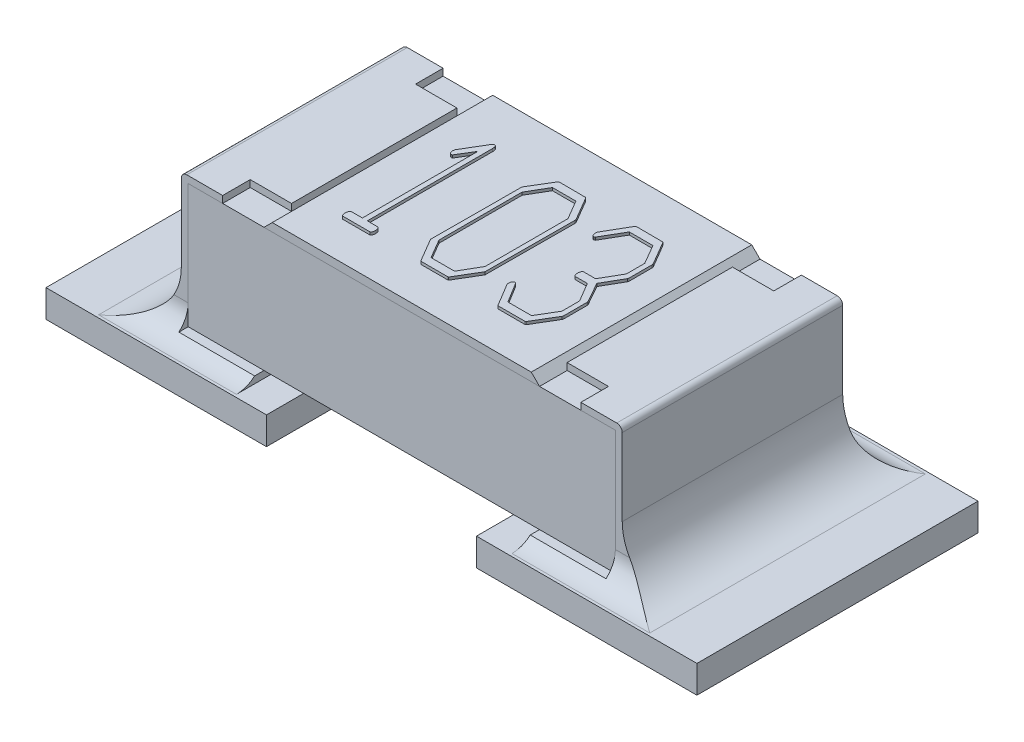
SolidWorks part; units mm, degrees
material "Ceramic Porcelain"
ref_plane "Front Plane" through (0, 0, 0) normal (0, 0, 1) x (1, 0, 0)
ref_plane "Top Plane" through (0, 0, 0) normal (0, 1, 0) x (1, 0, 0)
ref_plane "Right Plane" through (0, 0, 0) normal (1, 0, 0) x (0, 0, -1)
sketch "Sketch1" plane through (0, 0, 0) normal (1, 0, 0) x (0, 0, -1)
  line L0 (0, 55) -> (0, -55) construction
  line L1 (-0.4, 0.575) -> (0.4, 0.575)
  line L2 (-0.4, 0.575) -> (-0.4, 0.125)
  line L3 (-0.4, 0.125) -> (0.4, 0.125)
  line L4 (0.4, 0.575) -> (0.4, 0.125)
  line L5 (55, 0) -> (-55, 0) construction
  dimension "D1" = 0.8
  dimension "D2" = 0.4
  dimension "D3" = 0.45
  dimension "D4" = 0.125
extrude "Boss-Extrude1" add sketch "Sketch1" along normal mid plane 1.55
sketch "Sketch2" plane through (0, 0, 0) normal (0, 0, 1) x (1, 0, 0)
  line L0 (-0.5, 0.6) -> (-0.78, 0.6)
  line L1 (-0.8, 0.58) -> (-0.8, 0.1)
  line L2 (-0.8, 0.1) -> (-0.5, 0.1)
  line L3 (-0.5, 0.1) -> (-0.5, 0.125)
  line L4 (0.775, 0.125) -> (-0.775, 0.125) construction
  line L5 (-0.5, 0.125) -> (-0.775, 0.125)
  line L6 (-0.775, 0.125) -> (-0.775, 0.575)
  line L7 (-0.775, 0.575) -> (-0.5, 0.575)
  line L8 (0.775, 0.575) -> (-0.775, 0.575) construction
  line L9 (-0.5, 0.575) -> (-0.5, 0.6)
  line L11 (0.5, 0.575) -> (0.5, 0.6)
  line L12 (0.5, 0.6) -> (0.78, 0.6)
  line L13 (0.8, 0.58) -> (0.8, 0.1)
  line L14 (0.8, 0.1) -> (0.5, 0.1)
  line L15 (0.5, 0.1) -> (0.5, 0.125)
  line L16 (0.5, 0.125) -> (0.775, 0.125)
  line L17 (0.775, 0.125) -> (0.775, 0.575)
  line L18 (0.775, 0.575) -> (0.5, 0.575)
  arc A0 (0.78, 0.6) -> (0.8, 0.58) centre (0.78, 0.58) cw
  arc A1 (-0.78, 0.6) -> (-0.8, 0.58) centre (-0.78, 0.58) ccw
  point P28 (-0.8, 0.6)
  dimension "D6" = 0.02
  dimension "D1" = 0.025
  dimension "D2" = 0.025
  dimension "D3" = 0.025
  dimension "D4" = 0.3
  dimension "D5" = 0.3
extrude "Boss-Extrude2" add sketch "Sketch2" along normal mid plane 0.8 separate body
sketch "Sketch3" plane through (0, 0.6, 0) normal (0, 1, 0) x (1, 0, 0)
  line L0 (0.5, -0.4) -> (0.5, 0.4) construction
  line L1 (-0.5, 0.4) -> (-0.65, 0.4)
  line L2 (-0.5, 0.4) -> (-0.5, 0.3)
  line L3 (-0.5, 0.3) -> (-0.65, 0.3)
  line L4 (-0.65, 0.4) -> (-0.65, 0.3)
  line L5 (-0.5, -0.4) -> (-0.65, -0.4)
  line L6 (-0.5, -0.4) -> (-0.5, -0.3)
  line L7 (-0.5, -0.3) -> (-0.65, -0.3)
  line L8 (-0.65, -0.4) -> (-0.65, -0.3)
  line L9 (0.5, -0.4) -> (0.65, -0.4)
  line L10 (0.5, -0.4) -> (0.5, -0.3)
  line L11 (0.5, -0.3) -> (0.65, -0.3)
  line L12 (0.65, -0.4) -> (0.65, -0.3)
  line L13 (0.775, -0.4) -> (-0.775, -0.4) construction
  line L15 (0.5, 0.4) -> (0.65, 0.4)
  line L16 (0.5, 0.4) -> (0.5, 0.3)
  line L17 (0.5, 0.3) -> (0.65, 0.3)
  line L18 (0.65, 0.4) -> (0.65, 0.3)
  dimension "D1" = 0.15
  dimension "D2" = 0.1
extrude "Cut-Extrude1" cut sketch "Sketch3" against normal blind 0.025
sketch "Sketch4" plane through (0, 0, 0) normal (0, 0, 1) x (1, 0, 0)
  line L0 (-0.5, 0.575) -> (0.5, 0.575)
  line L1 (0.5, 0.575) -> (0.47, 0.605)
  line L2 (0.47, 0.605) -> (-0.47, 0.605)
  line L3 (-0.47, 0.605) -> (-0.5, 0.575)
  dimension "D1" = 45
  dimension "D2" = 45
  dimension "D3" = 0.03
extrude "Boss-Extrude3" add sketch "Sketch4" along normal mid plane 0.8 separate body
sketch "Sketch6" plane through (0, 0.605, 0) normal (0, 1, 0) x (1, 0, 0)
  line L0 (-0.4, -0.25) -> (0.4, -0.25) construction
  line L1 (0, -0.2777) -> (0, 0.2777) construction
  line L2 (-0.2777, 0) -> (0.2777, 0) construction
  text T0 "103\r\n" font "SWMono" height 0.5
  dimension "D1" = 0.8
  dimension "D2" = 0.4
  dimension "D3" = 0.25
extrude "Boss-Extrude4" add sketch "Sketch6" along normal blind 0.01
sketch "Sketch7" plane through (0, 0, 0) normal (0, 1, 0) x (1, 0, 0)
  line L0 (0, -0.2833) -> (0, 0.2833) construction
  line L1 (-0.381, -0.51) -> (-1.181, -0.51)
  line L2 (-0.381, -0.51) -> (-0.381, 0.51)
  line L3 (-0.381, 0.51) -> (-1.181, 0.51)
  line L4 (-1.181, -0.51) -> (-1.181, 0.51)
  line L5 (0.381, -0.51) -> (1.181, -0.51)
  line L6 (0.381, -0.51) -> (0.381, 0.51)
  line L7 (0.381, 0.51) -> (1.181, 0.51)
  line L8 (1.181, -0.51) -> (1.181, 0.51)
  line L9 (-0.2833, 0) -> (0.2833, 0) construction
  dimension "D1" = 0.8
  dimension "D2" = 0.381
  dimension "D3" = 0.381
  dimension "D4" = 1.02
  dimension "D5" = 0.51
extrude "Boss-Extrude5" add sketch "Sketch7" along normal blind 0.1
fillet "Fillet3" radius 0.2 1 edges at (-0.8, 0.1, 0)
fillet "Fillet4" radius 0.2 1 edges at (0.8, 0.1, 0)
fillet "Fillet5" radius 0.1 2 edges at (0.75, 0.1, -0.4) (0.75, 0.1, 0.4)
fillet "Fillet6" radius 0.1 2 edges at (-0.75, 0.1, 0.4) (-0.75, 0.1, -0.4)
